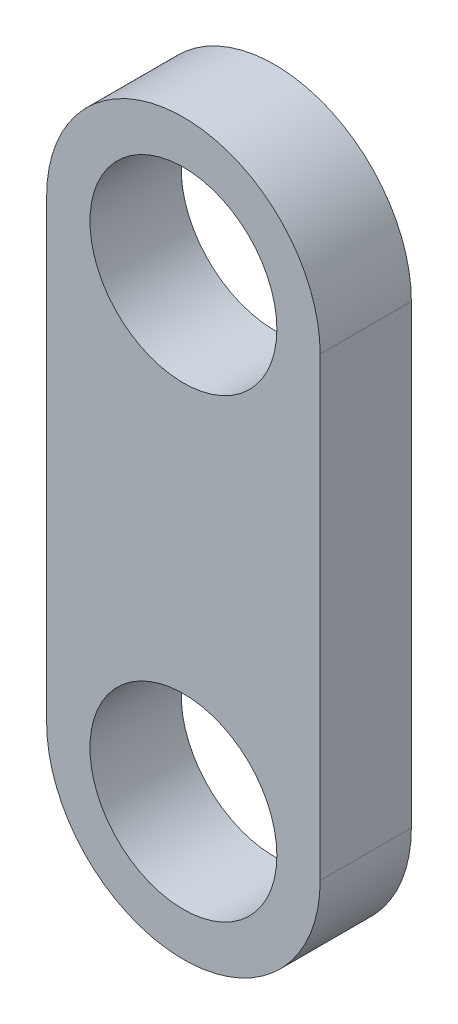
SolidWorks part; units mm, degrees
ref_plane "Front Plane" through (0, 0, 0) normal (0, 0, 1) x (1, 0, 0)
ref_plane "Top Plane" through (0, 0, 0) normal (0, 1, 0) x (1, 0, 0)
ref_plane "Right Plane" through (0, 0, 0) normal (1, 0, 0) x (0, 0, -1)
sketch "Sketch1" plane through (0, 0, 0) normal (0, 0, 1) x (1, 0, 0)
  line L0 (0, 0) -> (0, -50) construction
  line L1 (10.25, 0) -> (10.25, -50)
  line L2 (-10.25, 0) -> (-10.25, -50)
  line L3 (0, 0) -> (0, -50) construction
  line L4 (15, 0) -> (15, -50)
  line L5 (-15, 0) -> (-15, -50)
  arc A0 (10.25, 0) -> (-10.25, 0) centre (0, 0) ccw
  arc A1 (-10.25, -50) -> (10.25, -50) centre (0, -50) ccw
  arc A2 (15, 0) -> (-15, 0) centre (0, 0) ccw
  arc A3 (-15, -50) -> (15, -50) centre (0, -50) ccw
  circle A4 centre (0, -50) radius 10.25
  circle A5 centre (0, 0) radius 10.25
  point P3 (0, -25)
  point P10 (0, -25)
  dimension "D2" = 10.25
  dimension "D3" = 15
  dimension "D1" = 50
extrude "Boss-Extrude1" add sketch "Sketch1" along normal blind 10 contours L5 A3 L4 A2 A1 L2 A0 L1 | A5 L2 A4 L1 region at (0, -25, 0) region at (14.1456, -25, 0)
